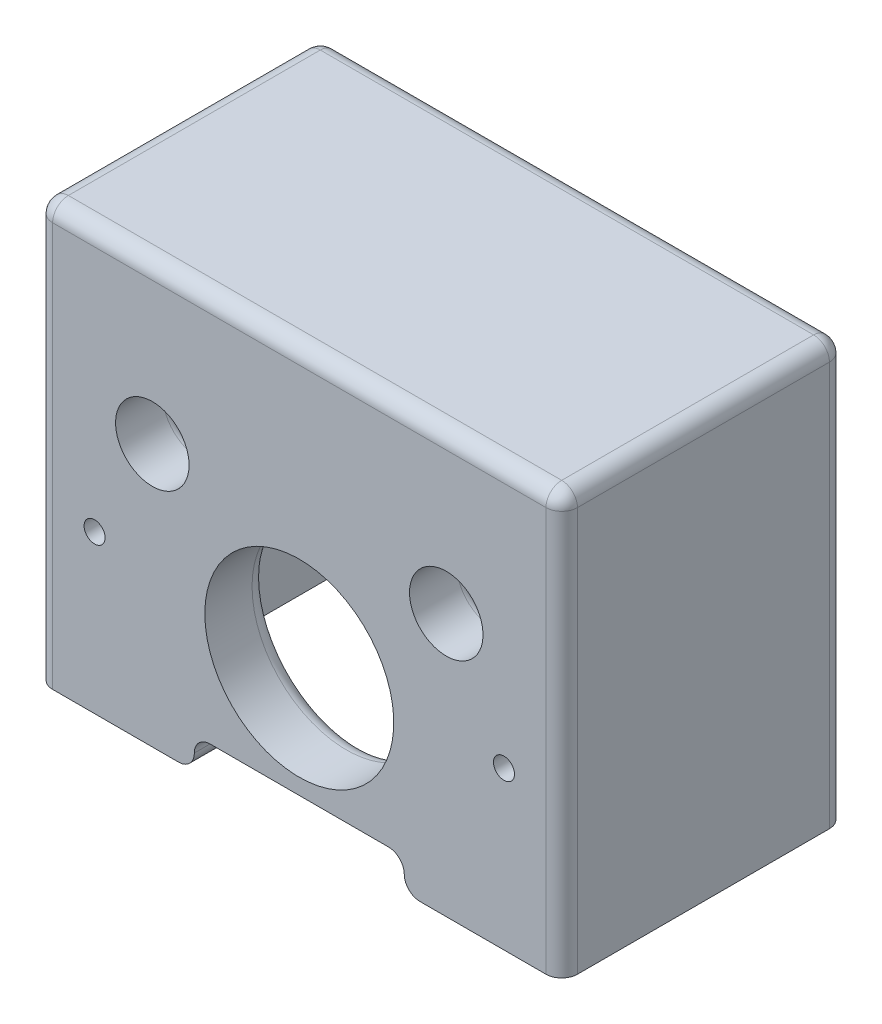
SolidWorks part; units mm, degrees
ref_plane "Front Plane" through (0, 0, 0) normal (0, 0, 1) x (1, 0, 0)
ref_plane "Top Plane" through (0, 0, 0) normal (0, 1, 0) x (1, 0, 0)
ref_plane "Right Plane" through (0, 0, 0) normal (1, 0, 0) x (0, 0, -1)
sketch "Sketch1" plane through (0, 0, 0) normal (0, 0, 1) x (1, 0, 0)
  line L1 (0, 0) -> (50, 0)
  line L2 (0, 0) -> (0, 40)
  line L3 (0, 40) -> (50, 40)
  line L4 (50, 0) -> (50, 40)
  dimension "D1" = 50
  dimension "D2" = 40
extrude "Boss-Extrude1" add sketch "Sketch1" along normal blind 27
sketch "Sketch2" plane through (0, 0, 0) normal (0, 0, -1) x (-1, 0, 0)
  line L0 (0, 0) -> (-50, 0) construction
  line L1 (-44.5, 0) -> (-5.5, 0)
  line L2 (-44.5, 0) -> (-44.5, 35)
  line L3 (-44.5, 35) -> (-5.5, 35)
  line L4 (-5.5, 0) -> (-5.5, 35)
  line L5 (-25, 40) -> (-25, 35) construction
  line L6 (-50, 40) -> (0, 40) construction
  dimension "D1" = 39
  dimension "D2" = 35
extrude "Cut-Extrude1" cut sketch "Sketch2" against normal blind 21
sketch "Sketch3" plane through (0, 0, 21) normal (0, 0, -1) x (-1, 0, 0)
  line L0 (-25, 35) -> (-25, 0) construction
  line L1 (-5.5, 35) -> (-44.5, 35) construction
  line L2 (-44.5, 0) -> (-5.5, 0) construction
  line L4 (-44.5, 25) -> (-5.5, 25) construction
  line L5 (-44.5, 35) -> (-44.5, 0) construction
  line L6 (-5.5, 0) -> (-5.5, 35) construction
  line L7 (-15, 0) -> (-15, 3)
  line L8 (-35, 0) -> (-15, 0)
  line L9 (-35, 0) -> (-35, 3)
  line L10 (-35, 3) -> (-15, 3)
  circle A0 centre (-25, 13.5) radius 9
  circle A1 centre (-39, 25) radius 3.5
  circle A2 centre (-11, 25) radius 3.5
  point P21 (0, 0)
  point P23 (-25, 3)
  dimension "D1" = 18
  dimension "D4" = 7
  dimension "D2" = 21.5
  dimension "D3" = 10
  dimension "D5" = 5.5
  dimension "D6" = 3
  dimension "D7" = 10
extrude "Cut-Extrude2" cut sketch "Sketch3" against normal through all
sketch "Sketch4" plane through (0, 0, 27) normal (0, 0, 1) x (1, 0, 0)
  line L0 (0, 13.5) -> (50, 13.5) construction
  line L1 (0, 40) -> (0, 0) construction
  line L2 (50, 0) -> (50, 40) construction
  line L3 (25, 40) -> (25, 22.5) construction
  line L4 (50, 40) -> (0, 40) construction
  circle A0 centre (44.5, 15) radius 1
  circle A1 centre (25, 13.5) radius 9 construction
  circle A2 centre (5.5, 15) radius 1
  dimension "D2" = 2
  dimension "D1" = 19.5
extrude "Cut-Extrude3" cut sketch "Sketch4" against normal up to surface (6 mm away) up to face at (14.5, 25, 21)
fillet "Fillet1" radius 1.5 21 edges at (15, 0, 24) (15, 3, 24) (35, 0, 24) (35, 3, 24) (15, 1.5, 21) (35, 1.5, 21) (25, 3, 21) (35.5, 25, 21) (14.5, 25, 21) (16, 13.5, 21) (5.5, 17.5, 0) (25, 35, 0) (44.5, 17.5, 0) (50, 20, 0) (0, 20, 0) (25, 40, 0) (0, 40, 13.5) (0, 20, 27) (25, 40, 27) (50, 20, 27) (50, 40, 13.5)
